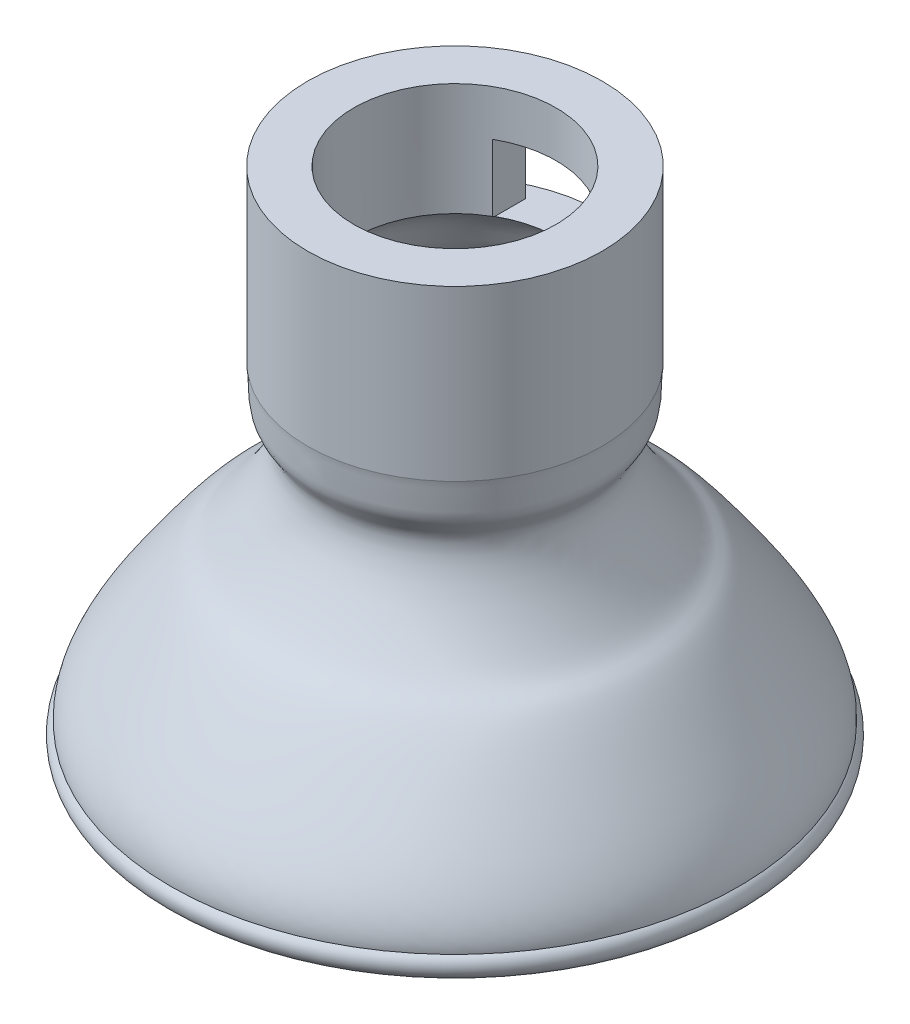
SolidWorks part; units mm, degrees
ref_plane "Plano frontal" through (0, 0, 0) normal (0, 0, 1) x (1, 0, 0)
ref_plane "Plano superior" through (0, 0, 0) normal (0, 1, 0) x (1, 0, 0)
ref_plane "Plano direito" through (0, 0, 0) normal (1, 0, 0) x (0, 0, -1)
sketch "Esboço1" plane through (0, 0, 0) normal (0, 0, 1) x (1, 0, 0)
  line L0 (23.6138, 12.9658) -> (23.1798, 12.9658)
  line L1 (12.4936, 41.6466) -> (12.4936, 41.4599)
  line L2 (8.5759, 46.237) -> (8.5759, 55.7804)
  line L3 (0, 44.5174) -> (0, 20.7069) construction
  line L4 (0, -55) -> (0, 55) construction
  line L5 (8.5759, 55.7804) -> (12.4936, 55.7804)
  line L6 (12.4936, 46.237) -> (12.4936, 55.7804)
  line L7 (12.4936, 46.237) -> (12.4936, 41.6466)
  arc A0 (22.8836, 15.0236) -> (23.1798, 12.9658) centre (23.3968, 14.0472) ccw
  arc A1 (23.6138, 12.9658) -> (24.0786, 14.9142) centre (23.3968, 14.0472) ccw
  spline S0 degree 3 poles (12.4936, 41.4599) (12.3013, 40.1984) (12.6727, 38.2323) (9.8982, 35.8696) (14.8595, 27.8084) (16.0899, 28.0208) (19.3542, 24.143) (24.2566, 16.8596) (24.0786, 14.9142) knots 0 0 0 0 0.101005 0.17504 0.372875 0.603292 0.835962 1 1 1 1
  spline S1 degree 1 poles (11.3073, 41.6408) (22.8836, 15.0236) knots 0 0 1 1 construction
  spline S2 degree 3 poles (11.3073, 41.6408) (11.2735, 41.4191) (11.2251, 40.9574) (11.193, 40.1522) (11.194, 39.3041) (11.1106, 38.7771) (11.0298, 38.5851) (10.8756, 38.3307) (10.6328, 37.9932) (10.3379, 37.5542) (10.0436, 36.9657) (9.826, 36.0076) (9.9146, 34.8903) (10.2965, 33.5753) (10.8639, 32.2936) (11.7591, 30.6645) (12.9464, 28.9199) (13.9488, 27.6965) (14.8014, 26.9604) (15.4187, 26.5771) (15.8418, 26.2557) (16.5896, 25.4893) (17.6296, 24.2205) (19.0007, 22.3695) (20.5444, 20.2008) (21.7129, 18.3359) (22.303, 17.2067) (22.6379, 16.3823) (22.8087, 15.8292) (22.8908, 15.3468) (22.8943, 15.1404) (22.8836, 15.0236) knots 0 0 0 0 0.015625 0.03125 0.0625 0.09375 0.109375 0.125 0.140625 0.15625 0.171875 0.1875 0.21875 0.25 0.28125 0.3125 0.375 0.4375 0.5 0.5625 0.625 0.6875 0.75 0.8125 0.875 0.90625 0.9375 0.953125 0.96875 0.984375 1 1 1 1
  spline S3 degree 3 poles (11.3073, 41.6408) (10.4933, 43.2397) (10.3322, 45.294) (8.5759, 46.237) knots 0 0 0 0 1 1 1 1
  dimension "D1" = 1.2
revolve "Revolução1" add sketch "Esboço1" angle 360 about L3
sketch "Esboço2" plane through (0, 0, 0) normal (0, 0, 1) x (1, 0, 0)
  line L0 (0, -21.0905) -> (0, 21.0905) construction
  line L1 (4.2604, 46.1353) -> (-4.2604, 46.1353)
  line L2 (4.2604, 46.1353) -> (4.2604, 51.8993)
  line L3 (4.2604, 51.8993) -> (-4.2604, 51.8993)
  line L4 (-4.2604, 46.1353) -> (-4.2604, 51.8993)
  line L5 (4.2604, 46.1353) -> (-4.2604, 51.8993) construction
  line L6 (4.2604, 51.8993) -> (-4.2604, 46.1353) construction
  point P0 (0, 49.0173)
extrude "Corte-extrusão1" cut sketch "Esboço2" against normal blind 21
sketch "Esboço3" plane through (0, 0, 0) normal (1, 0, 0) x (0, 0, -1)
  line L1 (12.4936, 51.8993) -> (10.2498, 51.8993)
  line L2 (12.4936, 51.8993) -> (12.4936, 46.1353)
  line L3 (12.4936, 46.1353) -> (10.2498, 46.1353)
  line L4 (10.2498, 51.8993) -> (10.2498, 46.1353)
extrude "Corte-extrusão2" cut sketch "Esboço3" against normal blind 21 and the other way blind 21
